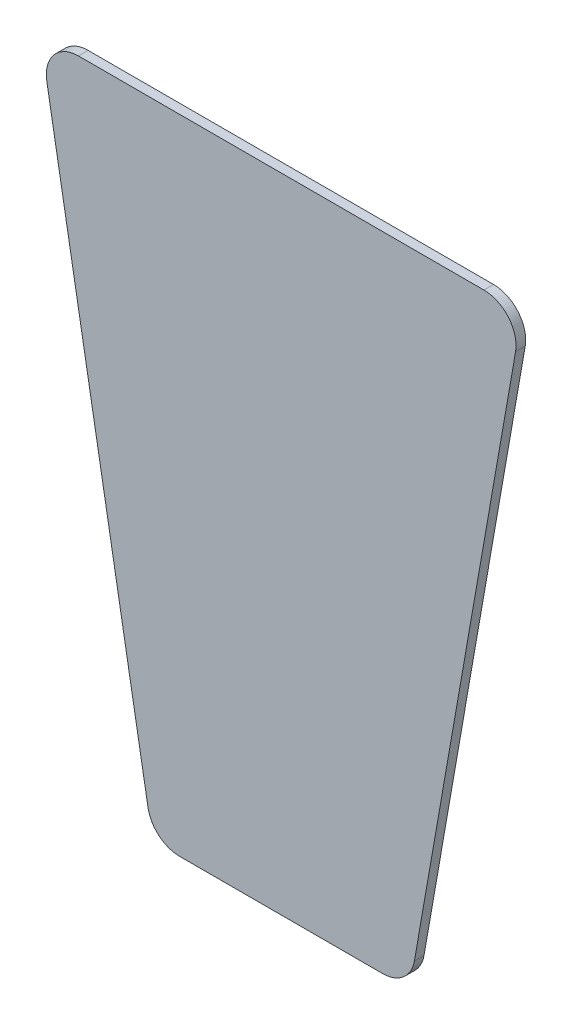
SolidWorks part; units mm, degrees
ref_plane "Front Plane" through (0, 0, 0) normal (0, 0, 1) x (1, 0, 0)
ref_plane "Top Plane" through (0, 0, 0) normal (0, 1, 0) x (1, 0, 0)
ref_plane "Right Plane" through (0, 0, 0) normal (1, 0, 0) x (0, 0, -1)
sketch "Sketch1" plane through (0, 0, 0) normal (0, 0, 1) x (1, 0, 0)
  line L0 (-40, 0) -> (40, 0)
  line L1 (0, 0) -> (0, 200) construction
  line L2 (-75, 200) -> (75, 200)
  line L3 (-75, 200) -> (-40, 0)
  line L4 (75, 200) -> (40, 0)
  point P4 (0, 0)
  point P10 (0, 200)
  dimension "D1" = 80
  dimension "D2" = 200
  dimension "D3" = 150
extrude "Boss-Extrude1" add sketch "Sketch1" along normal blind 3
fillet "Fillet1" radius 10 1 edges at (75, 200, 1.5) type face fillet first side face at (0, 200, 1.5) second side face at (57.5, 100, 1.5)
fillet "Fillet2" radius 10 1 edges at (40, 0, 1.5) type face fillet first side face at (56.4742, 94.1381, 1.5) second side face at (0, 0, 1.5)
fillet "Fillet3" radius 10 1 edges at (-40, 0, 1.5) type face fillet first side face at (-4.201, 0, 1.5) second side face at (-57.5, 100, 1.5)
fillet "Fillet4" radius 10 1 edges at (-75, 200, 1.5) type face fillet first side face at (-58.2242, 104.1381, 1.5) second side face at (-5.951, 200, 1.5)
